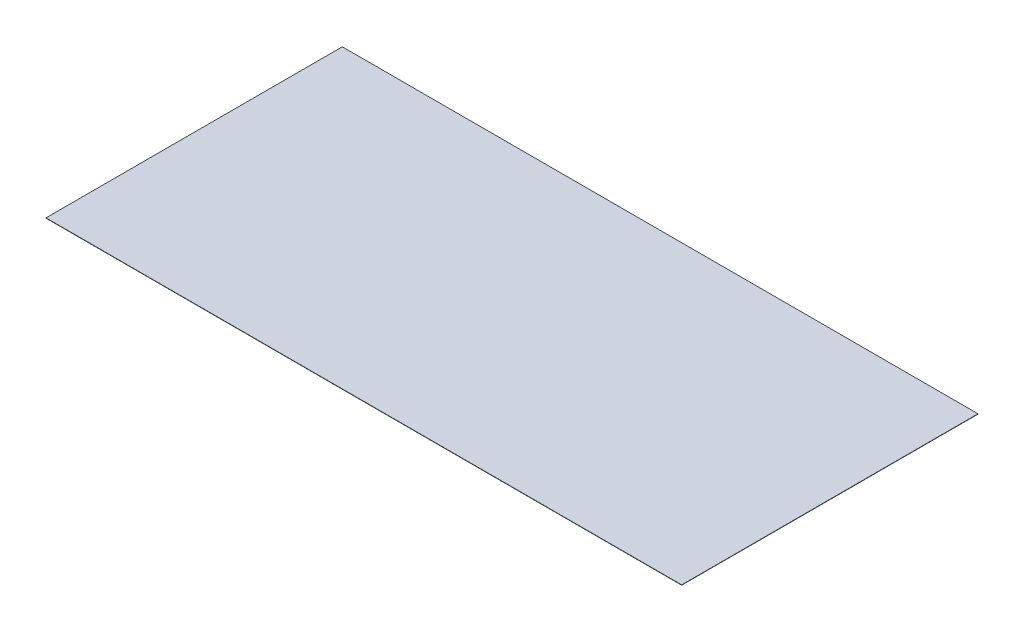
SolidWorks part; units mm, degrees
ref_plane "Front Plane" through (0, 0, 0) normal (0, 0, 1) x (1, 0, 0)
ref_plane "Top Plane" through (0, 0, 0) normal (0, 1, 0) x (1, 0, 0)
ref_plane "Right Plane" through (0, 0, 0) normal (1, 0, 0) x (0, 0, -1)
sketch "Sketch1" plane through (0, 0, 0) normal (0, 1, 0) x (1, 0, 0)
  line L1 (-408.686, -190.5) -> (408.686, -190.5)
  line L2 (-408.686, -190.5) -> (-408.686, 190.5)
  line L3 (-408.686, 190.5) -> (408.686, 190.5)
  line L4 (408.686, -190.5) -> (408.686, 190.5)
  line L5 (-408.686, -190.5) -> (408.686, 190.5) construction
  line L6 (-408.686, 190.5) -> (408.686, -190.5) construction
  point P0 (0, 0)
  dimension "D1" = 817.372
  dimension "D2" = 381
extrude "Boss-Extrude1" add sketch "Sketch1" along normal blind 0.4
